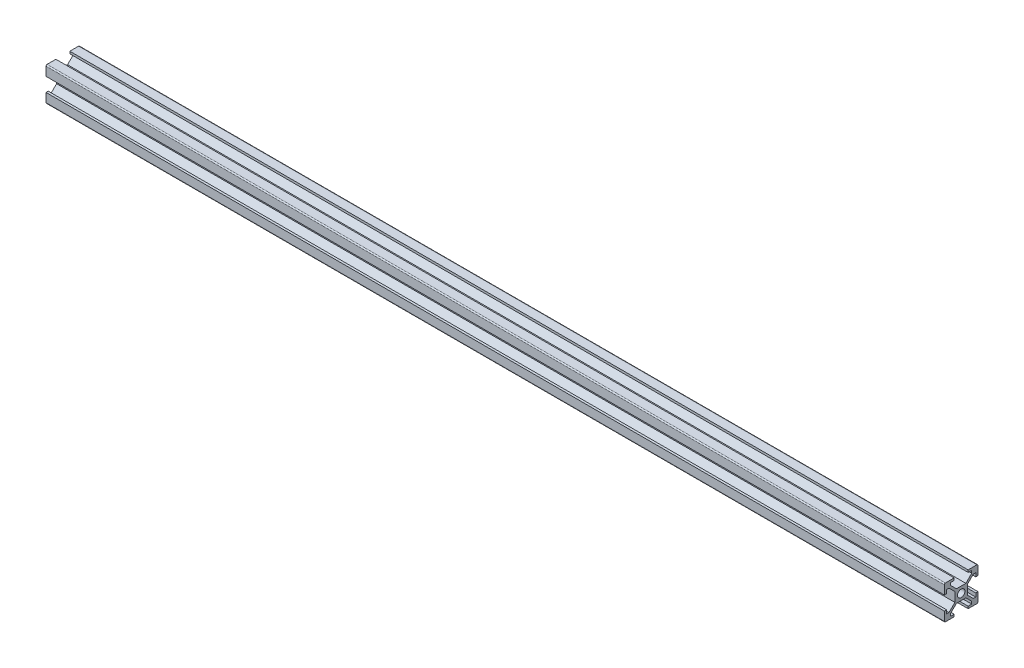
SolidWorks part; units mm, degrees
ref_plane "前视基准面" through (0, 0, 0) normal (0, 0, 1) x (1, 0, 0)
ref_plane "上视基准面" through (0, 0, 0) normal (0, 1, 0) x (1, 0, 0)
ref_plane "右视基准面" through (0, 0, 0) normal (1, 0, 0) x (0, 0, -1)
sketch "草图2" plane through (0, 0, 0) normal (1, 0, 0) x (0, 0, -1)
  line L0 (-3.1, 7.5) -> (3.1, 7.5)
  line L1 (-7, 7.5) -> (7, 7.5)
  line L2 (-7.5, 7) -> (-7.5, -7)
  line L3 (-7, -7.5) -> (7, -7.5)
  line L4 (7.5, 7) -> (7.5, -7)
  line L5 (-3.1, 7.5) -> (-3.1, 6.5)
  line L6 (-3.1, 6.5) -> (-4.7, 6.5)
  line L7 (-4.7, 6.5) -> (-4.7, 5.4071)
  line L8 (-4.7, 5.4071) -> (-2.0929, 2.8)
  line L9 (-2.0929, 2.8) -> (2.0929, 2.8)
  line L10 (2.0929, 2.8) -> (4.7, 5.4071)
  line L11 (4.7, 5.4071) -> (4.7, 6.5)
  line L12 (4.7, 6.5) -> (3.1, 6.5)
  line L13 (3.1, 6.5) -> (3.1, 7.5)
  line L14 (-7.5, -7.5) -> (7.5, 7.5) construction
  line L15 (7.5, -7.5) -> (-7.5, 7.5) construction
  line L17 (-2.8, 2.8) -> (2.8, 2.8)
  line L18 (-2.8, 2.8) -> (-2.8, -2.8)
  line L19 (-2.8, -2.8) -> (2.8, -2.8)
  line L20 (2.8, 2.8) -> (2.8, -2.8)
  line L21 (-2.8, 2.8) -> (2.8, -2.8) construction
  line L22 (-2.8, -2.8) -> (2.8, 2.8) construction
  line L52 (7.5, 3.1) -> (7.5, -3.1)
  line L53 (6.5, -3.1) -> (7.5, -3.1)
  line L54 (6.5, -4.7) -> (6.5, -3.1)
  line L55 (5.4071, -4.7) -> (6.5, -4.7)
  line L56 (2.8, -2.0929) -> (5.4071, -4.7)
  line L57 (2.8, 2.0929) -> (2.8, -2.0929)
  line L58 (5.4071, 4.7) -> (2.8, 2.0929)
  line L59 (6.5, 4.7) -> (5.4071, 4.7)
  line L60 (6.5, 3.1) -> (6.5, 4.7)
  line L61 (7.5, 3.1) -> (6.5, 3.1)
  line L62 (3.1, -7.5) -> (-3.1, -7.5)
  line L63 (-3.1, -6.5) -> (-3.1, -7.5)
  line L64 (-4.7, -6.5) -> (-3.1, -6.5)
  line L65 (-4.7, -5.4071) -> (-4.7, -6.5)
  line L66 (-2.0929, -2.8) -> (-4.7, -5.4071)
  line L67 (2.0929, -2.8) -> (-2.0929, -2.8)
  line L68 (4.7, -5.4071) -> (2.0929, -2.8)
  line L69 (4.7, -6.5) -> (4.7, -5.4071)
  line L70 (3.1, -6.5) -> (4.7, -6.5)
  line L71 (3.1, -7.5) -> (3.1, -6.5)
  line L72 (-7.5, -3.1) -> (-7.5, 3.1)
  line L73 (-6.5, 3.1) -> (-7.5, 3.1)
  line L74 (-6.5, 4.7) -> (-6.5, 3.1)
  line L75 (-5.4071, 4.7) -> (-6.5, 4.7)
  line L76 (-2.8, 2.0929) -> (-5.4071, 4.7)
  line L77 (-2.8, -2.0929) -> (-2.8, 2.0929)
  line L78 (-5.4071, -4.7) -> (-2.8, -2.0929)
  line L79 (-6.5, -4.7) -> (-5.4071, -4.7)
  line L80 (-6.5, -3.1) -> (-6.5, -4.7)
  line L81 (-7.5, -3.1) -> (-6.5, -3.1)
  line L82 (0, 0) -> (2.0929, 2.8) construction
  line L83 (0, 0) -> (2.8, -2.0929) construction
  circle A0 centre (0, 0) radius 1.65
  circle A1 centre (-7, 7) radius 0.5 construction
  circle A2 centre (-7, -7) radius 0.5 construction
  circle A3 centre (7, -7) radius 0.5 construction
  circle A4 centre (7, 7) radius 0.5 construction
  arc A5 (7, 7.5) -> (7.5, 7) centre (7, 7) cw
  arc A6 (7, -7.5) -> (7.5, -7) centre (7, -7) ccw
  arc A7 (-7.5, -7) -> (-7, -7.5) centre (-7, -7) ccw
  arc A8 (-7, 7.5) -> (-7.5, 7) centre (-7, 7) ccw
  point P16 (0, 0)
  point P50 (0, 7.5)
  point P52 (7.5, 0)
  dimension "D3" = 3.3
  dimension "D12" = 1
  dimension "D13" = 1
  dimension "D14" = 1
  dimension "D15" = 1
  dimension "D16" = 0.5
  dimension "D1" = 15
  dimension "D2" = 6.2
  dimension "D4" = 5.6
  dimension "D5" = 9.4
  dimension "D6" = 0.5
  dimension "D7" = 0.5
  dimension "D8" = 4.7
  dimension "D9" = 1
  dimension "D10" = 4
  dimension "D11" = 90
extrude "凸台-拉伸1" add sketch "草图2" along normal blind 400 contours L2 A7 L3 A6 L4 A5 L1 A8
extrude "切除-拉伸2" cut sketch "草图2<4>" against normal through all and the other way through all contours L3 L71 L70 L69 L68 L19 L66 L65 L64 L63 | L2 L81 L80 L79 L78 L18 L76 L75 L74 L73 | L12 L13 L0 L5 L6 L7 L8 L9 L10 L11 | L4 L61 L60 L59 L58 L20 L56 L55 L54 L53 | A0 region at (0, 5.2713, 0) region at (0, 0, 5.2713) region at (0, 0, -5.2713) region at (0, -5.2713, 0) region at (0, 0, 0)
sketch "草图2<4>" plane through (0, 0, 0) normal (1, 0, 0) x (0, 0, -1) same geometry as "草图2"
